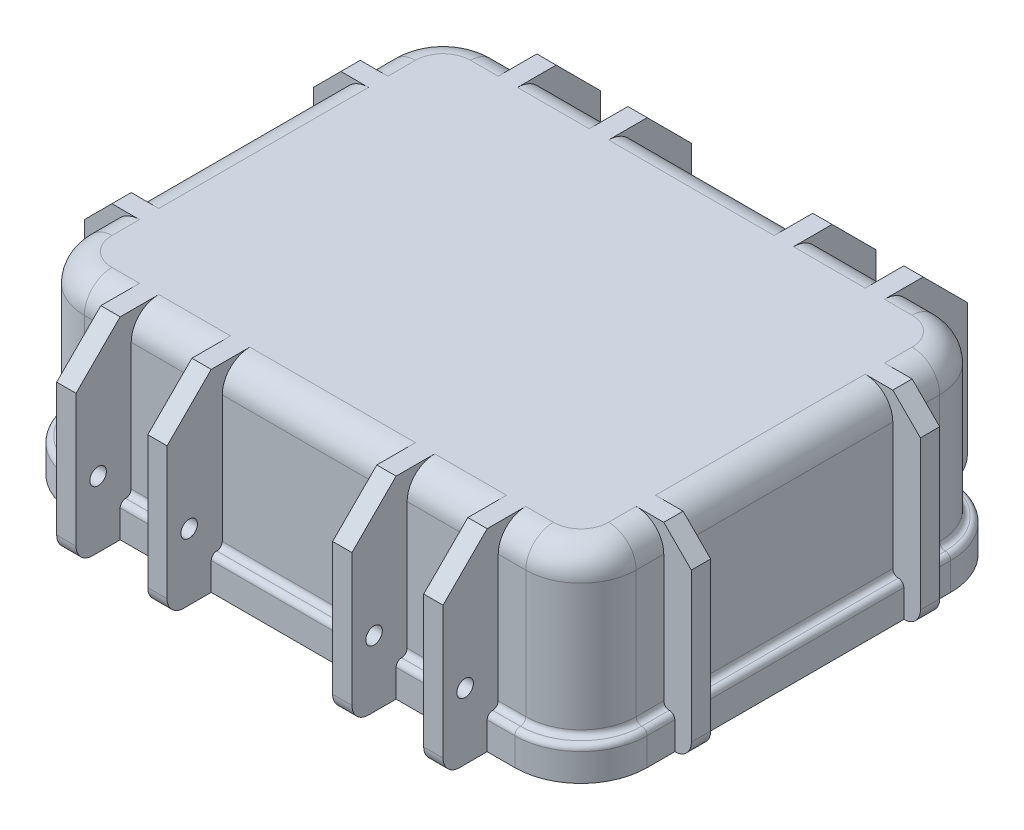
SolidWorks part; units mm, degrees
material "PUR"
ref_plane "Front Plane" through (0, 0, 0) normal (0, 0, 1) x (1, 0, 0)
ref_plane "Top Plane" through (0, 0, 0) normal (0, 1, 0) x (1, 0, 0)
ref_plane "Right Plane" through (0, 0, 0) normal (1, 0, 0) x (0, 0, -1)
sketch "Sketch1" plane through (0, 0, 0) normal (0, 1, 0) x (1, 0, 0)
  line L0 (-35, 37.5) -> (-35, 47.5)
  line L1 (40, -37.5) -> (-40, -37.5) construction
  line L2 (50, -27.5) -> (50, 27.5) construction
  line L3 (40, 37.5) -> (-40, 37.5) construction
  line L4 (-50, -27.5) -> (-50, 27.5) construction
  line L5 (50, -37.5) -> (-50, 37.5) construction
  line L6 (50, 37.5) -> (-50, -37.5) construction
  line L7 (-35, 47.5) -> (-31.5, 47.5)
  line L8 (-31.5, 47.5) -> (-31.5, 37.5)
  line L9 (-18.5, 37.5) -> (-18.5, 47.5)
  line L10 (-18.5, 47.5) -> (-15, 47.5)
  line L11 (-15, 47.5) -> (-15, 37.5)
  line L12 (-40, 37.5) -> (-35, 37.5)
  line L13 (-31.5, 37.5) -> (-18.5, 37.5)
  line L14 (0, -37.5) -> (0, 37.5) construction
  line L15 (40, 37.5) -> (35, 37.5)
  line L16 (35, 37.5) -> (35, 47.5)
  line L17 (35, 47.5) -> (31.5, 47.5)
  line L18 (15, 47.5) -> (15, 37.5)
  line L19 (18.5, 47.5) -> (15, 47.5)
  line L20 (18.5, 37.5) -> (18.5, 47.5)
  line L21 (31.5, 37.5) -> (18.5, 37.5)
  line L22 (31.5, 47.5) -> (31.5, 37.5)
  line L23 (-15, 37.5) -> (15, 37.5)
  line L24 (-50, 0) -> (50, 0) construction
  line L25 (-15, -37.5) -> (15, -37.5)
  line L26 (31.5, -47.5) -> (31.5, -37.5)
  line L27 (31.5, -37.5) -> (18.5, -37.5)
  line L28 (18.5, -37.5) -> (18.5, -47.5)
  line L29 (18.5, -47.5) -> (15, -47.5)
  line L30 (15, -47.5) -> (15, -37.5)
  line L31 (35, -47.5) -> (31.5, -47.5)
  line L32 (35, -37.5) -> (35, -47.5)
  line L33 (40, -37.5) -> (35, -37.5)
  line L34 (-31.5, -37.5) -> (-18.5, -37.5)
  line L35 (-40, -37.5) -> (-35, -37.5)
  line L36 (-15, -47.5) -> (-15, -37.5)
  line L37 (-18.5, -47.5) -> (-15, -47.5)
  line L38 (-18.5, -37.5) -> (-18.5, -47.5)
  line L39 (-31.5, -47.5) -> (-31.5, -37.5)
  line L40 (-35, -47.5) -> (-31.5, -47.5)
  line L41 (-35, -37.5) -> (-35, -47.5)
  line L42 (-50, 27.5) -> (-50, 22.5)
  line L43 (-50, 22.5) -> (-55, 22.5)
  line L44 (-55, 22.5) -> (-55, 19)
  line L45 (-55, 19) -> (-50, 19)
  line L46 (-55, -19) -> (-50, -19)
  line L47 (-55, -22.5) -> (-55, -19)
  line L48 (-50, -22.5) -> (-55, -22.5)
  line L49 (-50, -27.5) -> (-50, -22.5)
  line L50 (-50, 19) -> (-50, -19)
  line L51 (50, -27.5) -> (50, -22.5)
  line L52 (50, -22.5) -> (55, -22.5)
  line L53 (55, -22.5) -> (55, -19)
  line L54 (55, -19) -> (50, -19)
  line L55 (50, 19) -> (50, -19)
  line L56 (55, 19) -> (50, 19)
  line L57 (55, 22.5) -> (55, 19)
  line L58 (50, 22.5) -> (55, 22.5)
  line L59 (50, 27.5) -> (50, 22.5)
  arc A0 (-40, -37.5) -> (-50, -27.5) centre (-40, -27.5) cw
  arc A1 (40, -37.5) -> (50, -27.5) centre (40, -27.5) ccw
  arc A2 (50, 27.5) -> (40, 37.5) centre (40, 27.5) ccw
  arc A3 (-40, 37.5) -> (-50, 27.5) centre (-40, 27.5) ccw
  point P0 (0, 0)
  point P29 (0, 0)
  point P42 (0, 0)
  dimension "D3" = 10
  dimension "D1" = 100
  dimension "D2" = 75
  dimension "D4" = 3.5
  dimension "D6" = 13
  dimension "D7" = 10
  dimension "D5" = 5
  dimension "D8" = 5
  dimension "D9" = 5
  dimension "D10" = 3.5
extrude "Boss-Extrude1" add sketch "Sketch1" along normal blind 35
sketch "Sketch2" plane through (0, 0, 0) normal (0, 1, 0) x (1, 0, 0)
  line L0 (-40, 39.5) -> (40, 39.5)
  line L1 (-52, 27.5) -> (-52, -27.5)
  line L2 (-40, -39.5) -> (40, -39.5)
  line L3 (52, -27.5) -> (52, 27.5)
  line L52 (-55, -22.5) -> (-50, -22.5)
  line L53 (-50, -22.5) -> (-50, -27.5)
  line L54 (-40, -37.5) -> (-35, -37.5)
  line L55 (-35, -37.5) -> (-35, -47.5)
  line L56 (-35, -47.5) -> (-31.5, -47.5)
  line L57 (-31.5, -47.5) -> (-31.5, -37.5)
  line L58 (-31.5, -37.5) -> (-18.5, -37.5)
  line L59 (-18.5, -37.5) -> (-18.5, -47.5)
  line L60 (-18.5, -47.5) -> (-15, -47.5)
  line L61 (-15, -47.5) -> (-15, -37.5)
  line L62 (-15, -37.5) -> (15, -37.5)
  line L63 (15, -37.5) -> (15, -47.5)
  line L64 (15, -47.5) -> (18.5, -47.5)
  line L65 (18.5, -47.5) -> (18.5, -37.5)
  line L66 (18.5, -37.5) -> (31.5, -37.5)
  line L67 (31.5, -37.5) -> (31.5, -47.5)
  line L68 (31.5, -47.5) -> (35, -47.5)
  line L69 (35, -47.5) -> (35, -37.5)
  line L70 (35, -37.5) -> (40, -37.5)
  line L71 (50, -27.5) -> (50, -22.5)
  line L72 (50, -22.5) -> (55, -22.5)
  line L73 (55, -22.5) -> (55, -19)
  line L74 (55, -19) -> (50, -19)
  line L75 (50, -19) -> (50, 19)
  line L76 (50, 19) -> (55, 19)
  line L77 (55, 19) -> (55, 22.5)
  line L78 (55, 22.5) -> (50, 22.5)
  line L79 (50, 22.5) -> (50, 27.5)
  line L80 (40, 37.5) -> (35, 37.5)
  line L81 (35, 37.5) -> (35, 47.5)
  line L82 (35, 47.5) -> (31.5, 47.5)
  line L83 (31.5, 47.5) -> (31.5, 37.5)
  line L84 (31.5, 37.5) -> (18.5, 37.5)
  line L85 (18.5, 37.5) -> (18.5, 47.5)
  line L86 (18.5, 47.5) -> (15, 47.5)
  line L87 (15, 47.5) -> (15, 37.5)
  line L88 (15, 37.5) -> (-15, 37.5)
  line L89 (-15, 37.5) -> (-15, 47.5)
  line L90 (-15, 47.5) -> (-18.5, 47.5)
  line L91 (-18.5, 47.5) -> (-18.5, 37.5)
  line L92 (-18.5, 37.5) -> (-31.5, 37.5)
  line L93 (-31.5, 37.5) -> (-31.5, 47.5)
  line L94 (-31.5, 47.5) -> (-35, 47.5)
  line L95 (-35, 47.5) -> (-35, 37.5)
  line L96 (-35, 37.5) -> (-40, 37.5)
  line L97 (-50, 27.5) -> (-50, 22.5)
  line L98 (-50, 22.5) -> (-55, 22.5)
  line L99 (-55, 22.5) -> (-55, 19)
  line L100 (-55, 19) -> (-50, 19)
  line L101 (-50, 19) -> (-50, -19)
  line L102 (-50, -19) -> (-55, -19)
  line L103 (-55, -19) -> (-55, -22.5)
  line L104 (-55, -22.5) -> (-50, -22.5)
  line L105 (-50, -22.5) -> (-50, -27.5)
  line L106 (-40, -37.5) -> (-35, -37.5)
  line L107 (-35, -37.5) -> (-35, -47.5)
  line L108 (-35, -47.5) -> (-31.5, -47.5)
  line L109 (-31.5, -47.5) -> (-31.5, -37.5)
  line L110 (-31.5, -37.5) -> (-18.5, -37.5)
  line L111 (-18.5, -37.5) -> (-18.5, -47.5)
  line L112 (-18.5, -47.5) -> (-15, -47.5)
  line L113 (-15, -47.5) -> (-15, -37.5)
  line L114 (-15, -37.5) -> (15, -37.5)
  line L115 (15, -37.5) -> (15, -47.5)
  line L116 (15, -47.5) -> (18.5, -47.5)
  line L117 (18.5, -47.5) -> (18.5, -37.5)
  line L118 (18.5, -37.5) -> (31.5, -37.5)
  line L119 (31.5, -37.5) -> (31.5, -47.5)
  line L120 (31.5, -47.5) -> (35, -47.5)
  line L121 (35, -47.5) -> (35, -37.5)
  line L122 (35, -37.5) -> (40, -37.5)
  line L123 (50, -27.5) -> (50, -22.5)
  line L124 (50, -22.5) -> (55, -22.5)
  line L125 (55, -22.5) -> (55, -19)
  line L126 (55, -19) -> (50, -19)
  line L127 (50, -19) -> (50, 19)
  line L128 (50, 19) -> (55, 19)
  line L129 (55, 19) -> (55, 22.5)
  line L130 (55, 22.5) -> (50, 22.5)
  line L131 (50, 22.5) -> (50, 27.5)
  line L132 (40, 37.5) -> (35, 37.5)
  line L133 (35, 37.5) -> (35, 47.5)
  line L134 (35, 47.5) -> (31.5, 47.5)
  line L135 (31.5, 47.5) -> (31.5, 37.5)
  line L136 (31.5, 37.5) -> (18.5, 37.5)
  line L137 (18.5, 37.5) -> (18.5, 47.5)
  line L138 (18.5, 47.5) -> (15, 47.5)
  line L139 (15, 47.5) -> (15, 37.5)
  line L140 (15, 37.5) -> (-15, 37.5)
  line L141 (-15, 37.5) -> (-15, 47.5)
  line L142 (-15, 47.5) -> (-18.5, 47.5)
  line L143 (-18.5, 47.5) -> (-18.5, 37.5)
  line L144 (-18.5, 37.5) -> (-31.5, 37.5)
  line L145 (-31.5, 37.5) -> (-31.5, 47.5)
  line L146 (-31.5, 47.5) -> (-35, 47.5)
  line L147 (-35, 47.5) -> (-35, 37.5)
  line L148 (-35, 37.5) -> (-40, 37.5)
  line L149 (-50, 27.5) -> (-50, 22.5)
  line L150 (-50, 22.5) -> (-55, 22.5)
  line L151 (-55, 22.5) -> (-55, 19)
  line L152 (-55, 19) -> (-50, 19)
  line L153 (-50, 19) -> (-50, -19)
  line L154 (-50, -19) -> (-55, -19)
  line L155 (-55, -19) -> (-55, -22.5)
  arc A0 (-40, 39.5) -> (-52, 27.5) centre (-40, 27.5) ccw
  arc A1 (-52, -27.5) -> (-40, -39.5) centre (-40, -27.5) ccw
  arc A2 (40, -39.5) -> (52, -27.5) centre (40, -27.5) ccw
  arc A3 (52, 27.5) -> (40, 39.5) centre (40, 27.5) ccw
  arc A4 (-50, -27.5) -> (-40, -37.5) centre (-40, -27.5) ccw
  arc A5 (40, -37.5) -> (50, -27.5) centre (40, -27.5) ccw
  arc A6 (50, 27.5) -> (40, 37.5) centre (40, 27.5) ccw
  arc A7 (-40, 37.5) -> (-50, 27.5) centre (-40, 27.5) ccw
  arc A8 (-50, -27.5) -> (-40, -37.5) centre (-40, -27.5) ccw
  arc A9 (40, -37.5) -> (50, -27.5) centre (40, -27.5) ccw
  arc A10 (50, 27.5) -> (40, 37.5) centre (40, 27.5) ccw
  arc A11 (-40, 37.5) -> (-50, 27.5) centre (-40, 27.5) ccw
  dimension "D1" = 0
  dimension "D2" = 2
extrude "Boss-Extrude2" add sketch "Sketch2" along normal blind 6 contours L148 A11 L149 L150 L1 L152 L153 L154 L104 L105 A8 L106 L107 L2 L109 L110 L111 L113 L114 L115 L117 L118 L119 L121 L122 A9 L123 L124 L3 L126 L127 L128 L130 L131 A10 L132 L133 L0 L135 L136 L137 L139 L140 L141 | A1 L2 A2 L3 A3 L0 A0 L1 region at (0, 0, 0)
sketch "Sketch3" plane through (0, 0, 0) normal (1, 0, 0) x (0, 0, -1)
  line L0 (-43.5, 12) -> (43.5, 12) construction
  line L1 (-47.5, 35) -> (-47.5, 0) construction
  line L2 (-47.5, 35) -> (-47.5, 0) construction
  circle A0 centre (-43.5, 12) radius 1.5
  circle A1 centre (43.5, 12) radius 1.5
  point P7 (0, 12)
  dimension "D2" = 3
  dimension "D3" = 4
  dimension "D1" = 12
extrude "Cut-Extrude1" cut sketch "Sketch3" against normal blind 56 and the other way blind 56
chamfer "Chamfer1" distance 5 angle 45 4 edges at (55, 35, -20.75) (55, 35, 20.75) (-55, 35, 20.75) (-55, 35, -20.75)
chamfer "Chamfer2" distance 8 angle 45 8 edges at (33.25, 35, -47.5) (33.25, 35, 47.5) (16.75, 35, 47.5) (-16.75, 35, 47.5) (-33.25, 35, 47.5) (-33.25, 35, -47.5) (-16.75, 35, -47.5) (16.75, 35, -47.5)
fillet "Fillet3" radius 1 40 edges at (52, 6, 0) (50, 6, 0) (37.5, 6, 39.5) (52, 6, 25) (37.5, 6, 37.5) (50, 6, 25) (-52, 6, 25) (-37.5, 6, 39.5) (-50, 6, 25) (-37.5, 6, 37.5) (-37.5, 6, -39.5) (-52, 6, -25) (-37.5, 6, -37.5) (-50, 6, -25) (52, 6, -25) (37.5, 6, -39.5) (37.5, 6, -37.5) (47.0711, 6, -34.5711) (0, 6, 39.5) (0, 6, 37.5) (25, 6, 39.5) (25, 6, 37.5) (-25, 6, 39.5) (-25, 6, 37.5) (48.4853, 6, 35.9853) (47.0711, 6, 34.5711) (-48.4853, 6, 35.9853) (-47.0711, 6, 34.5711) (-52, 6, 0) (-50, 6, 0) (-48.4853, 6, -35.9853) (-47.0711, 6, -34.5711) (-25, 6, -39.5) (-25, 6, -37.5) (0, 6, -39.5) (0, 6, -37.5) (25, 6, -39.5) (25, 6, -37.5) (48.4853, 6, -35.9853) (50, 6, -25)
fillet "Fillet4" radius 3 12 edges at (55, 0, -20.75) (55, 0, 20.75) (33.25, 0, 47.5) (16.75, 0, 47.5) (-16.75, 0, 47.5) (-33.25, 0, 47.5) (-55, 0, 20.75) (-55, 0, -20.75) (-33.25, 0, -47.5) (-16.75, 0, -47.5) (16.75, 0, -47.5) (33.25, 0, -47.5)
fillet "Fillet6" radius 5 20 edges at (25, 35, -37.5) (37.5, 35, -37.5) (47.0711, 35, -34.5711) (50, 35, -25) (50, 35, 0) (50, 35, 25) (37.5, 35, 37.5) (47.0711, 35, 34.5711) (25, 35, 37.5) (0, 35, 37.5) (-25, 35, 37.5) (-37.5, 35, 37.5) (-50, 35, 25) (-47.0711, 35, 34.5711) (-50, 35, 0) (-50, 35, -25) (-37.5, 35, -37.5) (-47.0711, 35, -34.5711) (-25, 35, -37.5) (0, 35, -37.5) tangent propagation no
sketch "Sketch6" plane through (0, 0, 0) normal (0, -1, 0) x (1, 0, 0)
  line L44 (-40, 37.5) -> (40, 37.5)
  line L45 (-50, 27.5) -> (-50, -27.5)
  line L46 (-40, -37.5) -> (40, -37.5)
  line L47 (50, -27.5) -> (50, 27.5)
  line L48 (-40, 35.5) -> (40, 35.5)
  line L49 (48, -27.5) -> (48, 27.5)
  line L50 (-40, -35.5) -> (40, -35.5)
  line L51 (-48, 27.5) -> (-48, -27.5)
  arc A4 (-52, -27.5) -> (-40, -39.5) centre (-40, -27.5) ccw construction
  arc A5 (40, -39.5) -> (52, -27.5) centre (40, -27.5) ccw construction
  arc A6 (52, 27.5) -> (40, 39.5) centre (40, 27.5) ccw construction
  arc A7 (-40, 39.5) -> (-52, 27.5) centre (-40, 27.5) ccw construction
  arc A8 (-52, -27.5) -> (-40, -39.5) centre (-40, -27.5) ccw construction
  arc A9 (40, -39.5) -> (52, -27.5) centre (40, -27.5) ccw construction
  arc A10 (52, 27.5) -> (40, 39.5) centre (40, 27.5) ccw construction
  arc A11 (-40, 39.5) -> (-52, 27.5) centre (-40, 27.5) ccw construction
  arc A12 (-40, 37.5) -> (-50, 27.5) centre (-40, 27.5) ccw
  arc A13 (50, 27.5) -> (40, 37.5) centre (40, 27.5) ccw
  arc A14 (40, -37.5) -> (50, -27.5) centre (40, -27.5) ccw
  arc A15 (-50, -27.5) -> (-40, -37.5) centre (-40, -27.5) ccw
  arc A16 (48, 27.5) -> (40, 35.5) centre (40, 27.5) ccw
  arc A17 (40, -35.5) -> (48, -27.5) centre (40, -27.5) ccw
  arc A18 (-48, -27.5) -> (-40, -35.5) centre (-40, -27.5) ccw
  arc A19 (-40, 35.5) -> (-48, 27.5) centre (-40, 27.5) ccw
  dimension "D1" = 2
  dimension "D2" = 2
extrude "Cut-Extrude3" cut sketch "Sketch6" against normal blind 2
sketch "Sketch5" plane through (0, 0, 0) normal (0, -1, 0) x (1, 0, 0)
  line L0 (-40, 33.5) -> (40, 33.5)
  line L1 (-46, 27.5) -> (-46, -27.5)
  line L2 (-40, -33.5) -> (40, -33.5)
  line L3 (46, 27.5) -> (46, -27.5)
  arc A0 (-52, -27.5) -> (-40, -39.5) centre (-40, -27.5) ccw construction
  arc A1 (40, -39.5) -> (52, -27.5) centre (40, -27.5) ccw construction
  arc A2 (52, 27.5) -> (40, 39.5) centre (40, 27.5) ccw construction
  arc A3 (-40, 39.5) -> (-52, 27.5) centre (-40, 27.5) ccw construction
  arc A4 (-52, -27.5) -> (-40, -39.5) centre (-40, -27.5) ccw construction
  arc A5 (40, -39.5) -> (52, -27.5) centre (40, -27.5) ccw construction
  arc A6 (52, 27.5) -> (40, 39.5) centre (40, 27.5) ccw construction
  arc A7 (-40, 39.5) -> (-52, 27.5) centre (-40, 27.5) ccw construction
  arc A8 (-40, 33.5) -> (-46, 27.5) centre (-40, 27.5) ccw
  arc A9 (-46, -27.5) -> (-40, -33.5) centre (-40, -27.5) ccw
  arc A10 (40, -33.5) -> (46, -27.5) centre (40, -27.5) ccw
  arc A11 (46, 27.5) -> (40, 33.5) centre (40, 27.5) ccw
  dimension "D1" = 6
extrude "Cut-Extrude2" cut sketch "Sketch5" against normal offset from surface (20 mm away) 15 up to face at (0, 35, 0)
sketch "Sketch7" plane through (0, 20, 0) normal (0, -1, 0) x (1, 0, 0)
  line L0 (-29.5, 22) -> (-13, 22)
  line L1 (-13, 22) -> (-13, -22)
  line L2 (-13, -22) -> (-29.5, -22)
  line L3 (29.5, 22) -> (13, 22)
  line L4 (13, 22) -> (13, -22)
  line L5 (13, -22) -> (29.5, -22)
  line L6 (-13, 0) -> (13, 0) construction
  line L8 (-34.5, -22) -> (34.5, -22)
  line L9 (34.5, -22) -> (34.5, 22)
  line L10 (34.5, 22) -> (-34.5, 22)
  line L11 (-34.5, 22) -> (-34.5, -22)
  line L12 (-34.5, -22) -> (34.5, -22) construction
  line L13 (34.5, -17) -> (34.5, 17)
  line L14 (34.5, 22) -> (-34.5, 22) construction
  line L15 (-34.5, 17) -> (-34.5, -17)
  arc A1 (34.5, 17) -> (29.5, 22) centre (29.5, 17) ccw
  arc A2 (29.5, -22) -> (34.5, -17) centre (29.5, -17) ccw
  arc A4 (-29.5, -22) -> (-34.5, -17) centre (-29.5, -17) cw
  arc A7 (-29.5, 22) -> (-34.5, 17) centre (-29.5, 17) ccw
  point P7 (0, 0)
  dimension "D3" = 5
  dimension "D2" = 26
  dimension "D1" = 11.5
extrude "Cut-Extrude4" cut sketch "Sketch7" against normal blind 3
sketch "Sketch8" plane through (0, 23, 0) normal (0, -1, 0) x (1, 0, 0)
  line L0 (-23, 0) -> (23, 0) construction
  line L1 (-13, -22) -> (-13, 22) construction
  circle A0 centre (-23, 0) radius 1.8
  circle A1 centre (23, 0) radius 1.8
  point P4 (0, 0)
  dimension "D2" = 3.6
  dimension "D1" = 10
extrude "Cut-Extrude5" cut sketch "Sketch8" against normal blind 7
sketch "Sketch9" plane through (0, 0, 0) normal (1, 0, 0) x (0, 0, -1)
  line L0 (-19, 0) -> (19, 0) construction
  line L1 (-21.5, 20) -> (21.5, 20)
  line L3 (-22, 20) -> (22, 20) construction
  arc A0 (21.5, 20) -> (-21.5, 20) centre (0, 0) ccw
  dimension "D1" = 21.5
  dimension "D2" = 21.5
extrude "Cut-Extrude6" cut sketch "Sketch9" against normal blind 13 and the other way blind 13 contours L1 A0
equation "\"D8@Sketch1\"=\"D5@Sketch1\""
equation "\"D10@Sketch1\"=\"D4@Sketch1\""
equation "\"D2@Sketch9\"=\"D1@Sketch9\""
